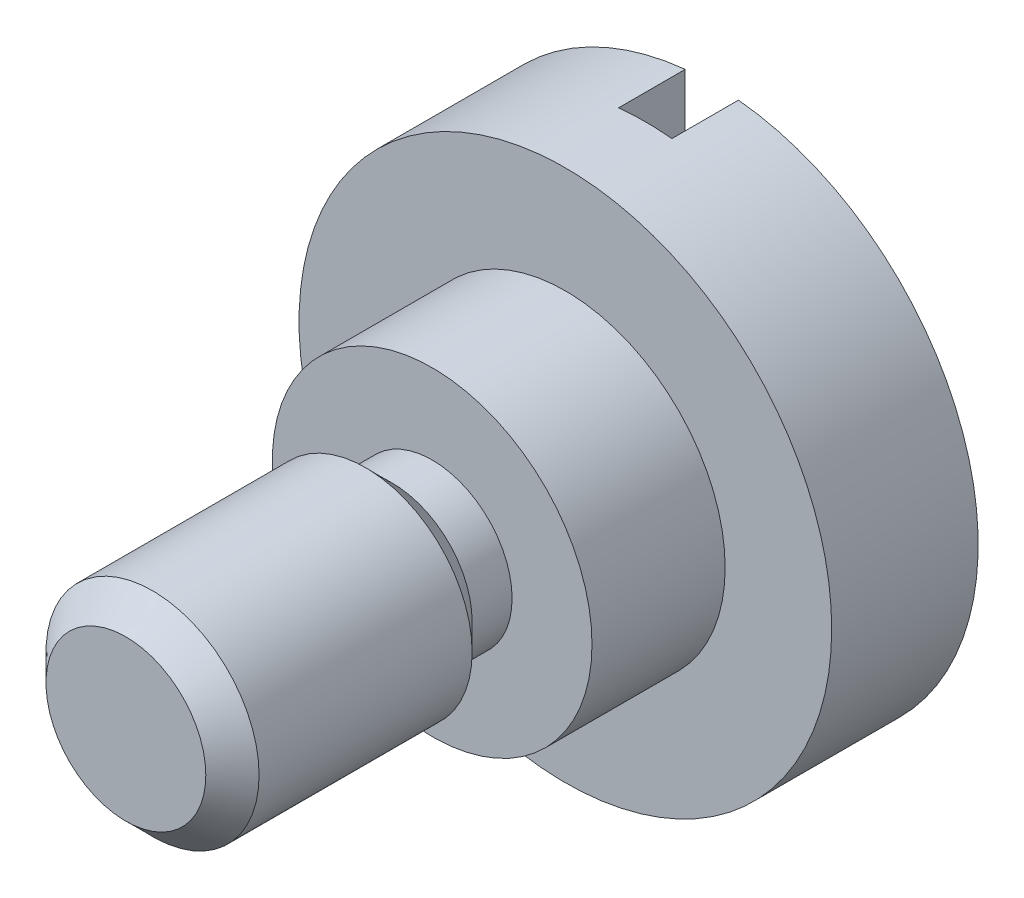
SolidWorks part; units mm, degrees
ref_plane "前视基准面" through (0, 0, 0) normal (0, 0, 1) x (1, 0, 0)
ref_plane "上视基准面" through (0, 0, 0) normal (0, 1, 0) x (1, 0, 0)
ref_plane "右视基准面" through (0, 0, 0) normal (1, 0, 0) x (0, 0, -1)
sketch "草图1" plane through (0, 0, 0) normal (0, 0, 1) x (1, 0, 0)
  circle A0 centre (0, 0) radius 10
  dimension "D1" = 20
extrude "凸台-拉伸1" add sketch "草图1" along normal blind 5.5
sketch "草图2" plane through (0, 0, 5.5) normal (0, 0, 1) x (1, 0, 0)
  circle A0 centre (0, 0) radius 6
  dimension "D1" = 12
extrude "凸台-拉伸2" add sketch "草图2" along normal blind 5
sketch "草图3" plane through (0, 0, 10.5) normal (0, 0, 1) x (1, 0, 0)
  circle A0 centre (0, 0) radius 3
  dimension "D1" = 6
extrude "凸台-拉伸3" add sketch "草图3" along normal blind 1.5
sketch "草图4" plane through (0, 0, 12) normal (0, 0, 1) x (1, 0, 0)
  circle A0 centre (0, 0) radius 4
  dimension "D1" = 8
extrude "凸台-拉伸4" add sketch "草图4" along normal blind 10
chamfer "倒角1" distance 1 angle 45 2 edges at (4, 0, 12) (4, 0, 22)
sketch "草图5" plane through (0, 0, 0) normal (0, 0, -1) x (-1, 0, 0)
  line L0 (0, 10) -> (0, -10)
  circle A0 centre (0, 0) radius 10 construction
extrude "切除-拉伸-薄壁1" cut sketch "草图5" against normal blind 2.5 thin thin type mid plane wall 2
